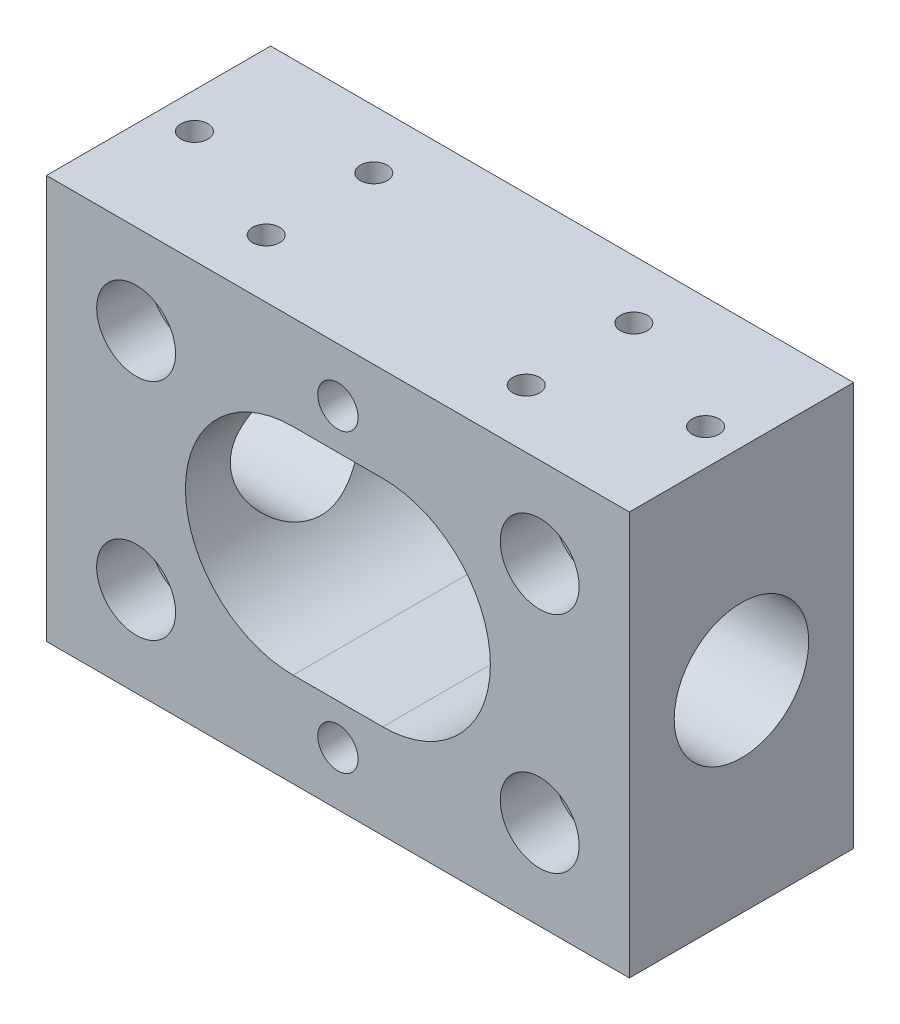
SolidWorks part; units mm, degrees
material "6061-T4 (SS)"
ref_plane "Piano frontale" through (0, 0, 0) normal (0, 0, 1) x (1, 0, 0)
ref_plane "Piano superiore" through (0, 0, 0) normal (0, 1, 0) x (1, 0, 0)
ref_plane "Piano destro" through (0, 0, 0) normal (1, 0, 0) x (0, 0, -1)
sketch "Schizzo1" plane through (0, 0, 0) normal (0, 0, 1) x (1, 0, 0)
  line L1 (0, 0) -> (65, 0)
  line L2 (0, 0) -> (0, 45)
  line L3 (0, 45) -> (65, 45)
  line L4 (65, 0) -> (65, 45)
  dimension "D1" = 65
  dimension "D2" = 45
extrude "Estrusione-Estrusione1" add sketch "Schizzo1" against normal blind 25
sketch "Schizzo2" plane through (0, 0, 0) normal (-1, 0, 0) x (0, 0, 1)
  line L0 (-25, 22.5) -> (0, 22.5) construction
  line L1 (-25, 45) -> (-25, 0) construction
  line L2 (0, 45) -> (0, 0) construction
  circle A0 centre (-12.5, 22.5) radius 7.5
  dimension "D1" = 15
extrude "Taglio-Estrusione1" cut sketch "Schizzo2" against normal through all
sketch "Schizzo3" plane through (0, 0, -25) normal (0, 0, -1) x (-1, 0, 0)
  line L0 (-60, 39) -> (4.9562, 39) construction
  line L2 (-65, 45) -> (0, 45) construction
  line L4 (-65, 22.5) -> (0, 22.5) construction
  line L5 (-65, 0) -> (-65, 45) construction
  line L6 (0, 45) -> (0, 0) construction
  line L7 (-60, 6) -> (4.9562, 6) construction
  line L8 (-32.5, 45) -> (-32.5, 0) construction
  line L9 (0, 0) -> (-65, 0) construction
  point P16 (-32.5, 39)
  point P17 (-32.5, 6)
  dimension "D1" = 6
hole_wizard "Foro lamato per Vite M4 a testa cilindrica piana-1" positions "Schizzo3D1" profile "Schizzo4" counterbore size "M4" standard "ISO" end condition through all
sketch3d "Schizzo3D1"
  point P0 (32.5, 39, -25)
  point P3 (32.5, 6, -25)
sketch "Schizzo4" plane through (32.5, 39, -25) normal (1, 0, 0) x (0, 1, 0)
  line L0 (0, 0) -> (0, 25)
  line L1 (0, 25) -> (2.25, 25)
  line L3 (2.25, 25) -> (2.25, 2.6)
  line L4 (2.25, 2.6) -> (4, 2.6)
  line L5 (4, 2.6) -> (4, 0)
  line L7 (4, 0) -> (0, 0)
  line L11 (0, -6.35) -> (0, 107.95) construction
  dimension "Thru Hole Dia." = 4.5
  dimension "Thru Hole Depth" = 25
  dimension "C'Bore Dia." = 8
  dimension "C'Bore Depth" = 2.6
ref_axis "Assi1" through (65, 22.5, -12.5) along (-1, 0, 0)
sketch "Schizzo14" plane through (0, 0, 0) normal (0, 0, 1) x (1, 0, 0)
  line L3 (37.5, 22.5) -> (27.5, 22.5) construction
  line L4 (65, 22.5) -> (0, 22.5) construction
  line L5 (37.5, 10.5) -> (27.5, 10.5)
  line L6 (37.5, 34.5) -> (27.5, 34.5)
  arc A0 (37.5, 10.5) -> (37.5, 34.5) centre (37.5, 22.5) ccw
  arc A1 (27.5, 34.5) -> (27.5, 10.5) centre (27.5, 22.5) ccw
  point P10 (32.5, 22.5)
  dimension "D1" = 10
  dimension "D2" = 24
extrude "Taglio-Estrusione4" cut sketch "Schizzo14" against normal through all
sketch "Schizzo15" plane through (0, 0, 0) normal (0, 0, 1) x (1, 0, 0)
  line L2 (0, 45) -> (0, 0) construction
  line L4 (32.5, 0) -> (32.5, 45) construction
  line L5 (65, 45) -> (0, 45) construction
  line L6 (0, 22.5) -> (65, 22.5) construction
  circle A0 centre (10, 10) radius 4.4
  circle A1 centre (55, 10) radius 4.4
  circle A2 centre (55, 35) radius 4.4
  circle A3 centre (10, 35) radius 4.4
  dimension "D1" = 8.8
  dimension "D2" = 10
  dimension "D3" = 10
extrude "Taglio-Estrusione5" cut sketch "Schizzo15" against normal blind 6
sketch "Schizzo16" plane through (0, 0, -6) normal (0, 0, 1) x (1, 0, 0)
  line L0 (32.5, 45) -> (32.5, 0) construction
  line L1 (0, 22.5) -> (65, 22.5) construction
  line L2 (0, 45) -> (0, 0) construction
  circle A0 centre (10, 10) radius 3
  circle A1 centre (55, 10) radius 3
  circle A2 centre (55, 35) radius 3
  circle A3 centre (10, 35) radius 3
  dimension "D1" = 6
extrude "Taglio-Estrusione6" cut sketch "Schizzo16" against normal through all
sketch "Schizzo17" plane through (0, 0, -25) normal (0, 0, -1) x (-1, 0, 0)
  line L0 (-32.5, 45) -> (-32.5, 0.5122) construction
  line L1 (-65, 45) -> (0, 45) construction
  line L2 (-32.5, 45) -> (-32.5, 0) construction
  line L3 (0, 22.5) -> (-65, 22.5) construction
  circle A0 centre (-10, 10) radius 5
  circle A1 centre (-55, 10) radius 5
  circle A2 centre (-55, 35) radius 5
  circle A3 centre (-10, 35) radius 5
  dimension "D1" = 10
extrude "Taglio-Estrusione8" cut sketch "Schizzo17" against normal blind 10
sketch "Schizzo18" plane through (0, 45, 0) normal (0, 1, 0) x (1, 0, 0)
  line L0 (0, 12.5) -> (65, 12.5) construction
  line L1 (0, 25) -> (0, 0) construction
  line L2 (65, 25) -> (65, 0) construction
  line L3 (32.5, 25) -> (32.5, 0) construction
  line L4 (65, 25) -> (0, 25) construction
  line L5 (65, 0) -> (0, 0) construction
  point P0 (4, 12.5)
  point P1 (18, 18.5)
  point P4 (18, 6.5)
  point P5 (47, 6.5)
  point P16 (47, 18.5)
  point P17 (61, 12.5)
  dimension "D3" = 6
  dimension "D1" = 4
  dimension "D2" = 18
hole_wizard "Foro Ø3.0 (3)-1" positions "Schizzo3D2" profile "Schizzo19" hole size "Ø3.0" standard "ISO"
sketch3d "Schizzo3D2"
  point P0 (18, 45, -18.5)
  point P3 (18, 45, -6.5)
  point P6 (4, 45, -12.5)
  point P9 (47, 45, -18.5)
  point P12 (47, 45, -6.5)
  point P15 (61, 45, -12.5)
sketch "Schizzo19" plane through (18, 45, -18.5) normal (1, 0, 0) x (0, 0, 1)
  line L0 (0, 0) -> (0, 12.9013)
  line L1 (0, 12.9013) -> (1.5, 12)
  line L2 (1.5, 12) -> (1.5, 0)
  line L5 (1.5, 0) -> (0, 0)
  line L10 (0, 12.9013) -> (-1.5, 12) construction
  line L11 (0, -6.35) -> (0, 107.95) construction
  dimension "Hole Dia." = 3
  dimension "Hole Depth" = 12
  dimension "Drill Angle" = 118
sketch "Schizzo20" plane through (0, 0, 0) normal (0, -1, 0) x (1, 0, 0)
  line L0 (0, -12.5) -> (65, -12.5) construction
  line L1 (32.5, 0) -> (32.5, -25) construction
  point P8 (4, -12.5)
  point P9 (18, -6.5)
  point P11 (18, -18.5)
  point P13 (47, -6.5)
  point P15 (61, -12.5)
  point P17 (47, -18.5)
  point P19 (-24.9919, -2.1046)
hole_wizard "Foro Ø3.0 (3)-2" positions "Schizzo3D3" profile "Schizzo21" hole size "Ø3.0" standard "ISO"
sketch3d "Schizzo3D3"
  point P0 (18, 0, -6.5)
  point P3 (4, 0, -12.5)
  point P6 (18, 0, -18.5)
  point P9 (47, 0, -6.5)
  point P12 (47, 0, -18.5)
  point P15 (61, 0, -12.5)
sketch "Schizzo21" plane through (18, 0, -6.5) normal (1, 0, 0) x (0, 0, -1)
  line L0 (0, 0) -> (0, 12.9013)
  line L1 (0, 12.9013) -> (1.5, 12)
  line L2 (1.5, 12) -> (1.5, 0)
  line L5 (1.5, 0) -> (0, 0)
  line L10 (0, 12.9013) -> (-1.5, 12) construction
  line L11 (0, -6.35) -> (0, 107.95) construction
  dimension "Hole Dia." = 3
  dimension "Hole Depth" = 12
  dimension "Drill Angle" = 118
sketch "Schizzo22" plane through (0, 0, 0) normal (-1, 0, 0) x (0, 0, 1)
  line L0 (-20, 45) -> (-20, 0) construction
  line L1 (-25, 45) -> (0, 45) construction
  line L2 (-25, 0) -> (0, 0) construction
  circle A0 centre (-12.5, 22.5) radius 7.5 construction
  point P5 (-20, 41)
  point P6 (-20, 4)
  dimension "D1" = 4
  dimension "D2" = 4
hole_wizard "Foro Ø3.0 (3)-3" positions "Schizzo3D4" profile "Schizzo23" hole size "Ø3.0" standard "ISO"
sketch3d "Schizzo3D4"
  point P0 (0, 41, -20)
  point P3 (0, 4, -20)
sketch "Schizzo23" plane through (0, 41, -20) normal (0, 1, 0) x (0, 0, 1)
  line L0 (0, 0) -> (0, 12.9013)
  line L1 (0, 12.9013) -> (1.5, 12)
  line L2 (1.5, 12) -> (1.5, 0)
  line L5 (1.5, 0) -> (0, 0)
  line L10 (0, 12.9013) -> (-1.5, 12) construction
  line L11 (0, -6.35) -> (0, 107.95) construction
  dimension "Hole Dia." = 3
  dimension "Hole Depth" = 12
  dimension "Drill Angle" = 118
